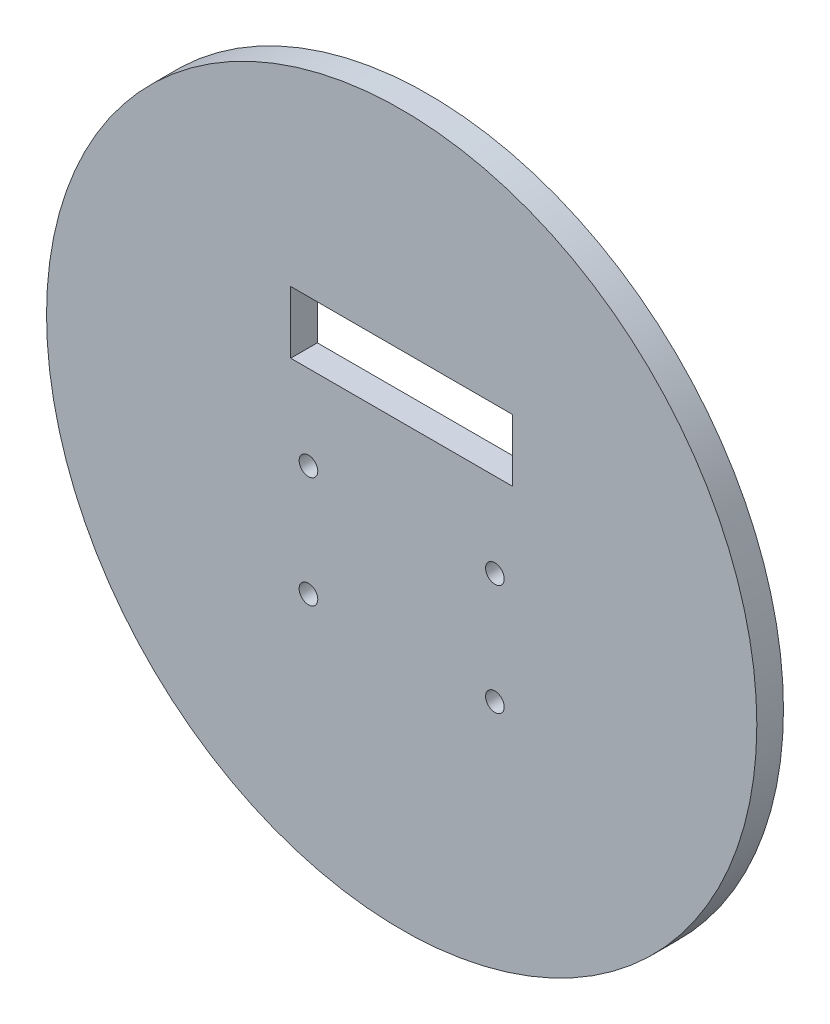
SolidWorks part; units mm, degrees
ref_plane "Plan de face" through (0, 0, 0) normal (0, 0, 1) x (1, 0, 0)
ref_plane "Plan de dessus" through (0, 0, 0) normal (0, 1, 0) x (1, 0, 0)
ref_plane "Plan de droite" through (0, 0, 0) normal (1, 0, 0) x (0, 0, -1)
sketch "Esquisse1" plane through (0, 0, 0) normal (0, 0, 1) x (1, 0, 0)
  line L0 (0, 0) -> (-10.5, 0) construction
  line L1 (-10.5, 0) -> (-10.5, -12.5) construction
  line L2 (-10.5, -12.5) -> (10.5, -12.5) construction
  line L3 (10.5, -12.5) -> (10.5, 0) construction
  line L4 (10.5, 0) -> (0, 0) construction
  circle A0 centre (0, 0) radius 40
  circle A1 centre (-10.5, -12.5) radius 1.05
  circle A2 centre (10.5, -12.5) radius 1.05
  circle A3 centre (-10.5, 0) radius 1.05
  circle A4 centre (10.5, 0) radius 1.05
  dimension "D1" = 80
  dimension "D6" = 2.1
  dimension "D7" = 2.1
  dimension "D8" = 2.1
  dimension "D9" = 2.1
  dimension "D2" = 10.5
  dimension "D3" = 10.5
  dimension "D4" = 12.5
  dimension "D5" = 21
extrude "Boss.-Extru.1" add sketch "Esquisse1" along normal blind 3
sketch "Esquisse2" plane through (0, 0, 0) normal (0, 0, 1) x (1, 0, 0)
  line L1 (12.5, 9.5) -> (-12.5, 9.5)
  line L2 (12.5, 9.5) -> (12.5, -14.5)
  line L3 (12.5, -14.5) -> (-12.5, -14.5)
  line L4 (-12.5, 9.5) -> (-12.5, -14.5)
  line L6 (0, 4) -> (0, -14.5)
  line L7 (12.5, 9.5) -> (-12.5, 9.5)
  line L8 (12.5, 9.5) -> (12.5, 16.5)
  line L9 (12.5, 16.5) -> (-12.5, 16.5)
  line L10 (-12.5, 9.5) -> (-12.5, 16.5)
  line L11 (12.5, 9.5) -> (-12.5, 9.5)
  line L12 (12.5, 9.5) -> (12.5, 4)
  line L14 (-12.5, 9.5) -> (-12.5, 4)
  line L15 (12.5, 9.5) -> (-12.5, 9.5)
  line L16 (12.5, 9.5) -> (12.5, 4)
  line L17 (12.5, 4) -> (-12.5, 4)
  line L18 (-12.5, 9.5) -> (-12.5, 4)
  circle A0 centre (10.5, -12.5) radius 1.05 construction
  dimension "D1" = 24
  dimension "D2" = 25
  dimension "D3" = 2
  dimension "D4" = 2
  dimension "D5" = 25
  dimension "D6" = 7
  dimension "D7" = 18.5
extrude "Enlèv. mat.-Extru.4" cut sketch "Esquisse2" along normal blind 14 contours L10 L1 L8 L9 region at (0, 13, 0)
extrude "Boss.-Extru.6" add sketch "Esquisse2<7>" against normal blind 2 contours L17 L2 L1 L4 region at (0, 6.75, 0)
sketch "Esquisse2<7>" plane through (0, 0, 0) normal (0, 0, 1) x (1, 0, 0) same geometry as "Esquisse2"
extrude "Enlèv. mat.-Extru.5" cut sketch "Esquisse2<8>" against normal blind 2 contours L17 L2 L1 L4 region at (0, 6.75, 0)
sketch "Esquisse2<8>" plane through (0, 0, 0) normal (0, 0, 1) x (1, 0, 0) same geometry as "Esquisse2"
extrude "Boss.-Extru.7" add sketch "Esquisse2<9>" against normal blind 2 contours L2 L17 L6 L3 | L6 L17 L4 L3 region at (6.25, -5.25, 0) region at (-6.25, -5.25, 0)
sketch "Esquisse2<9>" plane through (0, 0, 0) normal (0, 0, 1) x (1, 0, 0) same geometry as "Esquisse2"
sketch "Esquisse7" plane through (0, 0, 0) normal (0, 0, 1) x (1, 0, 0)
  circle A0 centre (-10.5, 0) radius 1.05
  circle A1 centre (-10.5, -12.5) radius 1.05
  circle A2 centre (10.5, 0) radius 1.05
  circle A3 centre (10.5, -12.5) radius 1.05
  dimension "D1" = 2.1
  dimension "D2" = 2.1
  dimension "D3" = 2.1
  dimension "D4" = 2.1
extrude "Enlèv. mat.-Extru.6" cut sketch "Esquisse7" against normal through all both and the other way through all
